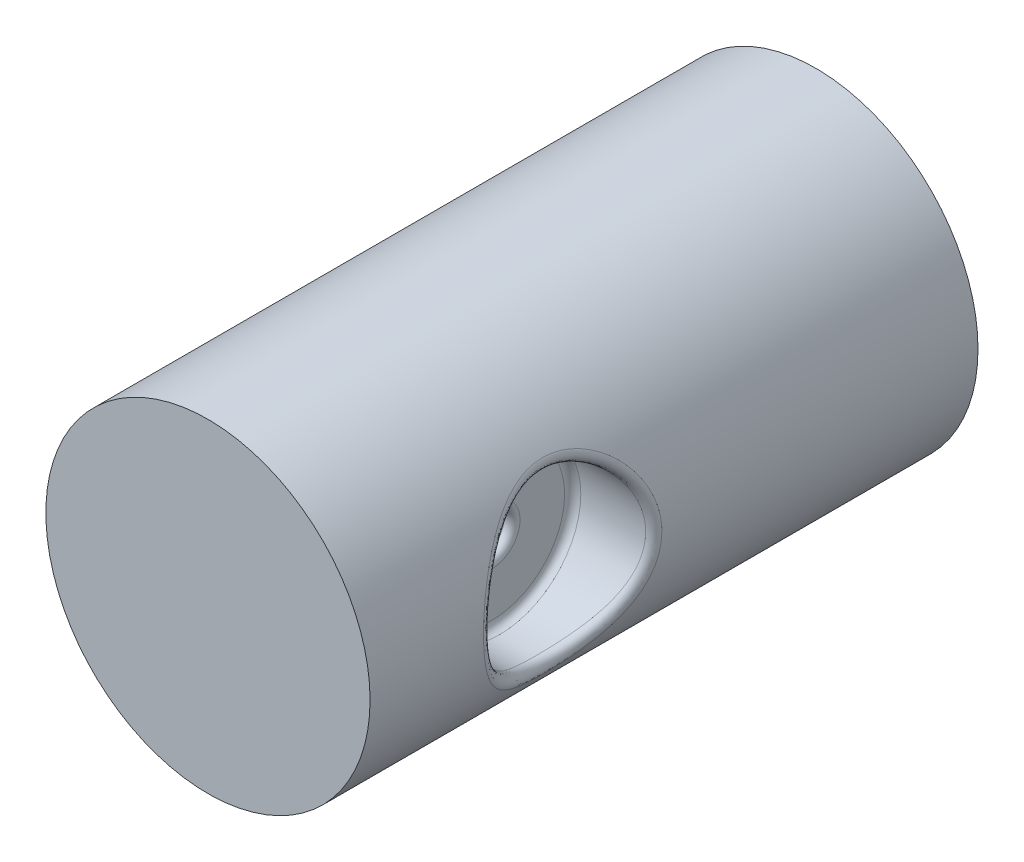
SolidWorks part; units mm, degrees
ref_plane "Front Plane" through (0, 0, 0) normal (0, 0, 1) x (1, 0, 0)
ref_plane "Top Plane" through (0, 0, 0) normal (0, 1, 0) x (1, 0, 0)
ref_plane "Right Plane" through (0, 0, 0) normal (1, 0, 0) x (0, 0, -1)
sketch "Sketch1" plane through (0, 0, 0) normal (0, 0, 1) x (1, 0, 0)
  circle A0 centre (0, 0) radius 20
  dimension "D1" = 40
extrude "Boss-Extrude1" add sketch "Sketch1" along normal blind 75
ref_plane "Plane1" through (20, 0, 0) normal (1, 0, 0) x (0, 0, -1)
sketch "Sketch2" plane through (20, 0, 0) normal (1, 0, 0) x (0, 0, -1)
  line L0 (-75, 20) -> (-75, -20) construction
  circle A0 centre (-50, 0) radius 10
  point P4 (0, 0)
  dimension "D1" = 20
  dimension "D2" = 25
extrude "Cut-Extrude1" cut sketch "Sketch2" against normal blind 10
sketch "Sketch3" plane through (20, 0, 0) normal (1, 0, 0) x (0, 0, -1)
  circle A0 centre (-50, 0) radius 2.5
  circle A1 centre (-50, 0) radius 10 construction
  dimension "D1" = 0
  dimension "D2" = 5
extrude "Cut-Extrude2" cut sketch "Sketch3" against normal blind 20
fillet "Fillet1" radius 1 4 edges at (0, 0, 47.5) (10, 0, 47.5) (19.9745, 1.0091, 59.949) (10, 0, 40)
sketch "Sketch4" plane through (0, 0, 0) normal (0, 0, -1) x (-1, 0, 0)
  line L0 (0, 20) -> (0, 0) construction
  line L1 (0, 0) -> (-20, 0) construction
  line L2 (-20, 22) -> (-20, -22) construction
  circle A0 centre (0, 0) radius 20 construction
